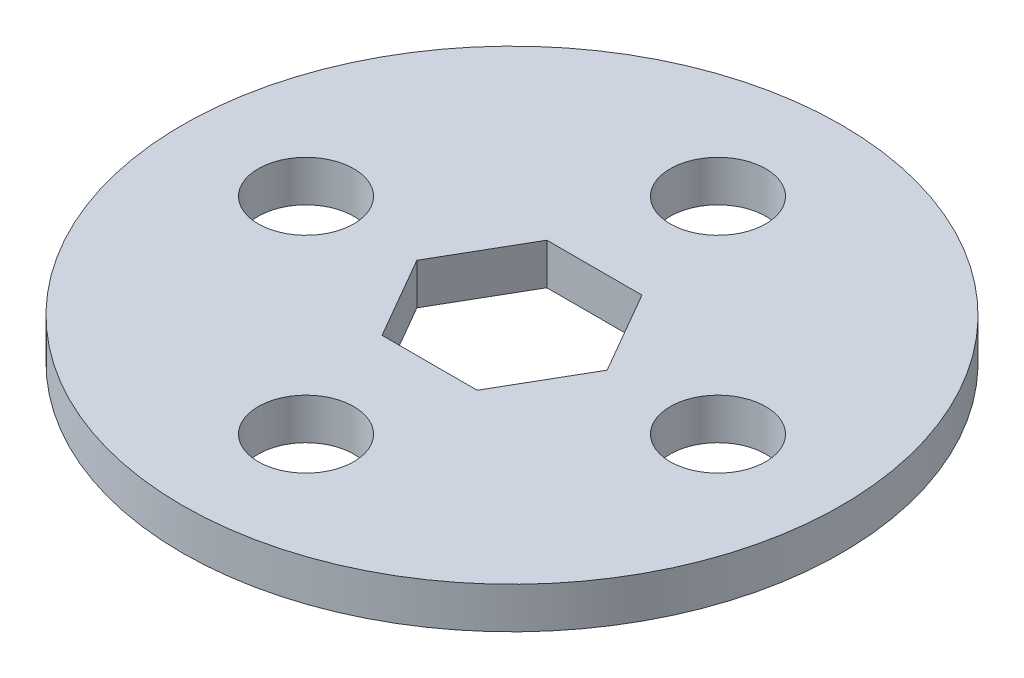
SolidWorks part; units mm, degrees
ref_plane "Front Plane" through (0, 0, 0) normal (0, 0, 1) x (1, 0, 0)
ref_plane "Top Plane" through (0, 0, 0) normal (0, 1, 0) x (1, 0, 0)
ref_plane "Right Plane" through (0, 0, 0) normal (1, 0, 0) x (0, 0, -1)
sketch "Sketch1" plane through (0, 0, 0) normal (0, 1, 0) x (1, 0, 0)
  line L0 (0, 25.4) -> (0, 6.35) construction
  line L1 (-7.3323, 0) -> (-3.6662, -6.35)
  line L2 (-3.6662, -6.35) -> (3.6662, -6.35)
  line L3 (3.6662, -6.35) -> (7.3323, 0)
  line L4 (7.3323, 0) -> (3.6662, 6.35)
  line L5 (3.6662, 6.35) -> (-3.6662, 6.35)
  line L6 (-3.6662, 6.35) -> (-7.3323, 0)
  circle A0 centre (0, 0) radius 25.4
  circle A1 centre (0, 0) radius 6.35 construction
  circle A2 centre (0, 15.875) radius 3.683
  circle A3 centre (15.875, 0) radius 3.683
  circle A4 centre (0, -15.875) radius 3.683
  circle A5 centre (-15.875, 0) radius 3.683
  point P23 (0, 0)
  dimension "D2" = 50.8
  dimension "D3" = 7.366
  dimension "D1" = 12.7
  dimension "D4" = 4
extrude "Boss-Extrude1" add sketch "Sketch1" along normal blind 3.175
